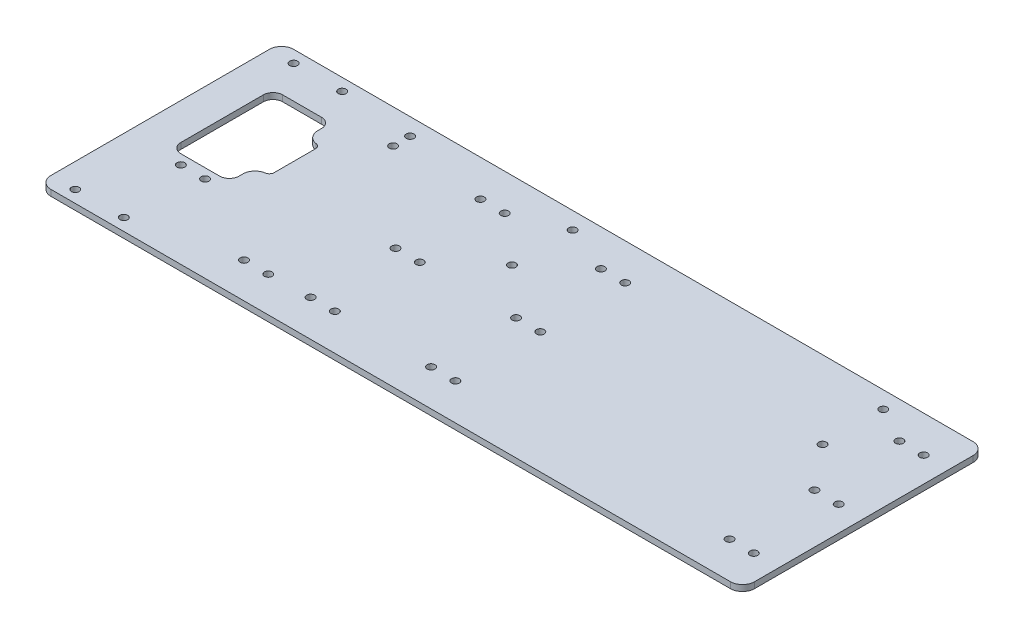
SolidWorks part; units mm, degrees
ref_plane "Front Plane" through (0, 0, 0) normal (0, 0, 1) x (1, 0, 0)
ref_plane "Top Plane" through (0, 0, 0) normal (0, 1, 0) x (1, 0, 0)
ref_plane "Right Plane" through (0, 0, 0) normal (1, 0, 0) x (0, 0, -1)
sketch "Sketch1" plane through (0, 0, 0) normal (0, 1, 0) x (1, 0, 0)
  line L0 (171.0189, 63.5) -> (171.0189, 44.45) construction
  line L1 (184.15, 63.5) -> (-184.15, 63.5)
  line L2 (184.15, 63.5) -> (184.15, -63.5)
  line L3 (184.15, -63.5) -> (-184.15, -63.5)
  line L4 (-184.15, 63.5) -> (-184.15, -63.5)
  line L5 (184.15, 63.5) -> (-184.15, -63.5) construction
  line L6 (184.15, -63.5) -> (-184.15, 63.5) construction
  line L7 (-128.2684, -0.635) -> (-128.2684, 31.115) construction
  line L8 (-128.2684, 31.115) -> (-134.6184, 31.115) construction
  line L9 (-128.2684, 5.715) -> (-134.6184, 5.715) construction
  line L12 (-165.0984, -13.335) -> (-165.0984, 40.005)
  line L15 (-134.6184, -13.335) -> (-165.0984, -13.335)
  line L17 (-134.6184, 40.005) -> (-165.0984, 40.005)
  line L18 (0, 63.5) -> (0, -63.5) construction
  line L19 (-134.6184, 40.005) -> (-134.6184, -13.335)
  line L20 (171.0189, 44.45) -> (184.15, 44.45) construction
  line L21 (0, 0) -> (-126.9984, 0) construction
  line L22 (-82.55, -45.0215) -> (-95.25, -45.0215) construction
  line L23 (171.0189, 44.45) -> (171.0189, 0) construction
  line L25 (171.0189, 0) -> (171.0189, -44.45) construction
  line L26 (171.0189, 44.45) -> (158.3189, 44.45) construction
  line L30 (171.0189, 0) -> (158.3189, 0) construction
  line L31 (171.0189, -44.45) -> (158.3189, -44.45) construction
  line L32 (158.3189, 44.45) -> (14.8089, 44.45) construction
  line L33 (14.8089, 44.45) -> (14.8089, 0) construction
  line L34 (14.8089, 0) -> (14.8089, -44.45) construction
  line L35 (-146.05, -57.15) -> (-184.15, -57.15) construction
  line L36 (-146.05, 57.15) -> (-184.15, 57.15) construction
  line L37 (-128.2684, -0.635) -> (-128.2684, 5.715) construction
  line L38 (-184.15, -18.415) -> (-154.94, -18.415) construction
  line L39 (-154.94, -18.415) -> (-142.24, -18.415) construction
  line L40 (-134.6184, 26.67) -> (-126.9984, 26.67)
  line L41 (-126.9984, 26.67) -> (-126.9984, 0)
  line L42 (-126.9984, 0) -> (-134.6184, 0)
  line L43 (14.8089, 44.45) -> (2.1089, 44.45) construction
  line L44 (14.8089, 0) -> (2.1089, 0) construction
  line L45 (14.8089, -44.45) -> (2.1089, -44.45) construction
  line L46 (2.1089, 44.45) -> (-48.2678, 44.45) construction
  line L47 (-48.2678, 44.45) -> (-60.9678, 44.45) construction
  line L48 (-48.2678, 44.45) -> (-48.2678, 0) construction
  line L49 (-48.2678, 0) -> (-60.9678, 0) construction
  line L50 (-48.2678, 0) -> (-48.2678, -44.45) construction
  line L51 (-48.2678, -44.45) -> (-60.9678, -44.45) construction
  circle A12 centre (-146.05, -57.15) radius 2.032
  circle A13 centre (-171.45, -57.15) radius 2.032
  circle A14 centre (-146.05, 57.15) radius 2.032
  circle A15 centre (-171.45, 57.15) radius 2.032
  circle A18 centre (-154.94, -18.415) radius 2.032
  circle A19 centre (-142.24, -18.415) radius 2.032
  circle A20 centre (-95.25, -45.0215) radius 2.032
  circle A21 centre (-82.55, -45.0215) radius 2.032
  circle A24 centre (171.0189, 44.45) radius 2.032
  circle A25 centre (171.0189, 0) radius 2.032
  circle A26 centre (171.0189, -44.45) radius 2.032
  circle A27 centre (158.3189, 44.45) radius 2.032
  circle A28 centre (158.3189, 0) radius 2.032
  circle A29 centre (158.3189, -44.45) radius 2.032
  circle A30 centre (2.1089, 44.45) radius 2.032
  circle A31 centre (2.1089, 0) radius 2.032
  circle A32 centre (2.1089, -44.45) radius 2.032
  circle A33 centre (14.8089, -44.45) radius 2.032
  circle A34 centre (14.8089, 0) radius 2.032
  circle A35 centre (14.8089, 44.45) radius 2.032
  circle A36 centre (-60.9678, 44.45) radius 2.032
  circle A37 centre (-48.2678, 44.45) radius 2.032
  circle A38 centre (-60.9678, 0) radius 2.032
  circle A39 centre (-60.9678, -44.45) radius 2.032
  circle A40 centre (-48.2678, -44.45) radius 2.032
  circle A41 centre (-48.2678, 0) radius 2.032
  point P0 (0, 0)
  point P11 (-128.2684, -0.635)
  point P13 (-134.6184, 31.115)
  point P17 (-134.6184, 5.715)
  point P37 (0, 0)
  dimension "D5" = 13.335
  dimension "D6" = 29.21
  dimension "D18" = 12.7
  dimension "D13" = 4.064
  dimension "D23" = 44.45
  dimension "D24" = 44.45
  dimension "D31" = 12.7
  dimension "D32" = 143.51
  dimension "D35" = 50.3767
  dimension "D1" = 368.3
  dimension "D2" = 127
  dimension "D3" = 128.27
  dimension "D4" = 25.4
  dimension "D7" = 6.35
  dimension "D8" = 30.48
  dimension "D9" = 53.34
  dimension "D10" = 8.89
  dimension "D11" = 19.05
  dimension "D12" = 12.7
  dimension "D14" = 38.1
  dimension "D15" = 6.35
  dimension "D16" = 12.7
  dimension "D17" = 6.35
  dimension "D19" = 31.75
  dimension "D20" = 19.05
  dimension "D21" = 13.1311
  dimension "D22" = 5.08
  dimension "D25" = 88.9
  dimension "D26" = 12.7
  dimension "D27" = 7.62
  dimension "D28" = 26.67
  dimension "D29" = 13.335
  dimension "D30" = 18.4785
  dimension "D33" = 44.45
  dimension "D34" = 44.45
extrude "Boss-Extrude1" add sketch "Sketch1" along normal blind 3.175 contours L1 L4 L3 L2 A21 A20 A18 A14 A12 L41 L42 L19 L15 L12 L17 L40 A13 A15 A19 region at (6.1738, 0, 0.5099)
fillet "Fillet1" radius 5.08 4 edges at (-134.6184, 1.5875, 13.335) (-165.0984, 1.5875, 13.335) (-165.0984, 1.5875, -40.005) (-134.6184, 1.5875, -40.005)
fillet "Fillet3" radius 6.35 4 edges at (184.15, 1.5875, 63.5) (184.15, 1.5875, -63.5) (-184.15, 1.5875, 63.5) (-184.15, 1.5875, -63.5)
fillet "Fillet4" radius 2.54 2 edges at (-126.9984, 1.5875, 0) (-126.9984, 1.5875, -26.67)
fillet "Fillet5" radius 6.35 2 edges at (-134.6184, 1.5875, 0) (-134.6184, 1.5875, -26.67)
sketch "Sketch2" plane through (0, 3.175, 0) normal (0, 1, 0) x (1, 0, 0)
  line L0 (-22.86, 54.61) -> (184.15, 54.61) construction
  line L2 (184.15, 57.15) -> (184.15, -57.15) construction
  line L3 (-22.86, 54.61) -> (-22.86, 22.86) construction
  line L4 (139.7, 54.61) -> (139.7, 22.86)
  line L5 (177.8, 63.5) -> (-177.8, 63.5) construction
  line L6 (-22.86, 54.61) -> (-107.95, 54.61) construction
  line L7 (-107.95, 54.61) -> (-107.95, 45.72) construction
  circle A0 centre (-22.86, 54.61) radius 2.032
  circle A1 centre (-22.86, 22.86) radius 2.032
  circle A2 centre (139.7, 54.61) radius 2.032
  circle A3 centre (139.7, 22.86) radius 2.032
  circle A4 centre (-107.95, 54.61) radius 2.032
  circle A5 centre (-107.95, 45.72) radius 2.032
  dimension "D5" = 4.064
  dimension "D6" = 8.89
  dimension "D1" = 207.01
  dimension "D2" = 31.75
  dimension "D3" = 44.45
  dimension "D4" = 8.89
  dimension "D7" = 292.1
extrude "Cut-Extrude1" cut sketch "Sketch2" against normal up to next contours A0 | A1 | A3 | A2 | A5 | A4 region at (141.0962, 3.175, -24.2562) region at (-22.86, 3.175, -54.61) region at (-22.86, 3.175, -22.86)
equation "\".80.55in\"=0.55"
